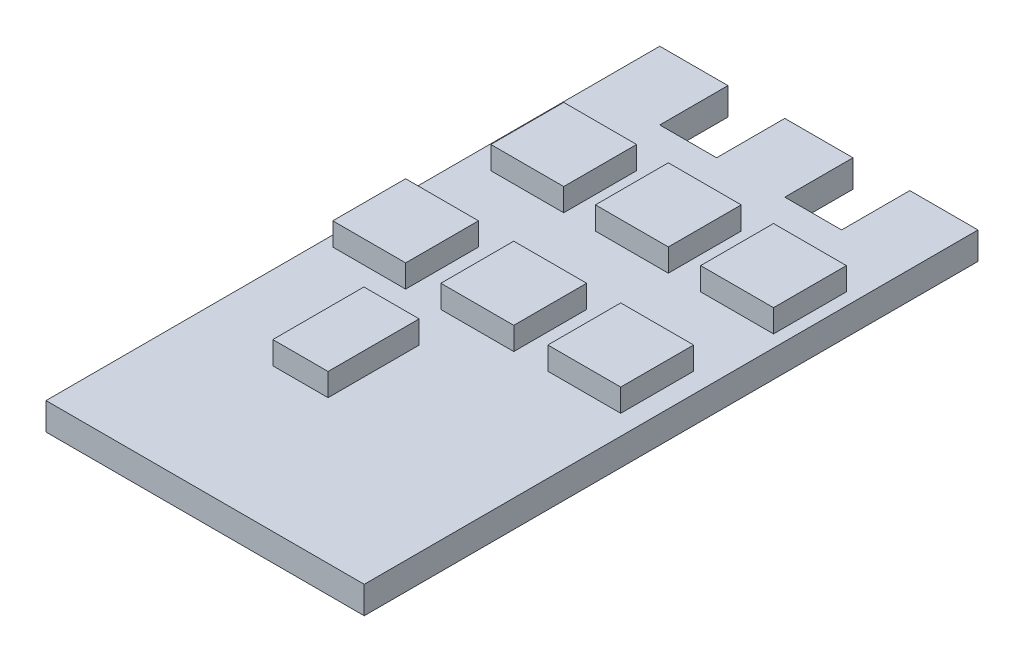
SolidWorks part; units mm, degrees
ref_plane "Front Plane" through (0, 0, 0) normal (0, 0, 1) x (1, 0, 0)
ref_plane "Top Plane" through (0, 0, 0) normal (0, 1, 0) x (1, 0, 0)
ref_plane "Right Plane" through (0, 0, 0) normal (1, 0, 0) x (0, 0, -1)
sketch "Sketch1" plane through (0, 0, 0) normal (0, 1, 0) x (1, 0, 0)
  line L0 (0, 21.6721) -> (0, -24.4888) construction
  line L1 (-7, 12) -> (7, 12)
  line L2 (-7, 12) -> (-7, -12)
  line L3 (-7, -12) -> (7, -12)
  line L4 (7, 12) -> (7, -12)
  line L5 (-7, 12) -> (7, -12) construction
  line L6 (-7, -12) -> (7, 12) construction
  line L8 (-1.5, 15) -> (1.5, 15)
  line L9 (-1.5, 15) -> (-1.5, 12)
  line L10 (-1.5, 12) -> (1.5, 12)
  line L11 (1.5, 15) -> (1.5, 12)
  line L12 (-1.5, 15) -> (1.5, 12) construction
  line L13 (-1.5, 12) -> (1.5, 15) construction
  line L14 (-7, 12) -> (-4, 12)
  line L15 (-7, 12) -> (-7, 15)
  line L16 (-7, 15) -> (-4, 15)
  line L17 (-4, 12) -> (-4, 15)
  line L18 (7, 12) -> (4, 12)
  line L19 (7, 12) -> (7, 15)
  line L20 (7, 15) -> (4, 15)
  line L21 (4, 12) -> (4, 15)
  point P0 (0, 0)
  point P7 (0, 13.5)
  dimension "D1" = 24
  dimension "D2" = 14
  dimension "D3" = 3
  dimension "D4" = 3
extrude "PCB" add sketch "Sketch1" along normal blind 1.2 contours L4 L1 L2 L3 | L1 L17 L16 L15 | L11 L8 L9 L1 | L21 L1 L19 L20 region at (-5.5, 0, -13.5) region at (0, 0, 0) region at (0, 0, -13.5) region at (5.5, 0, -13.5)
sketch "Sketch2" plane through (0, 1.2, 0) normal (0, 1, 0) x (1, 0, 0)
  line L1 (-5.9719, 9.747) -> (-2.7662, 9.747)
  line L2 (-5.9719, 9.747) -> (-5.9719, 6.5413)
  line L3 (-5.9719, 6.5413) -> (-2.7662, 6.5413)
  line L4 (-2.7662, 9.747) -> (-2.7662, 6.5413)
  line L5 (-1.3702, 9.747) -> (1.8355, 9.747)
  line L6 (-1.3702, 9.747) -> (-1.3702, 6.5413)
  line L7 (-1.3702, 6.5413) -> (1.8355, 6.5413)
  line L8 (1.8355, 9.747) -> (1.8355, 6.5413)
  line L9 (3.2574, 9.747) -> (6.4631, 9.747)
  line L10 (3.2574, 9.747) -> (3.2574, 6.5413)
  line L11 (3.2574, 6.5413) -> (6.4631, 6.5413)
  line L12 (6.4631, 9.747) -> (6.4631, 6.5413)
  line L13 (-3.335, 3.3614) -> (-6.5407, 3.3614)
  line L14 (-3.335, 3.3614) -> (-3.335, 0.1557)
  line L15 (-3.335, 0.1557) -> (-6.5407, 0.1557)
  line L16 (-6.5407, 3.3614) -> (-6.5407, 0.1557)
  line L17 (-1.7838, 3.3614) -> (1.4219, 3.3614)
  line L18 (-1.7838, 3.3614) -> (-1.7838, 0.1557)
  line L19 (-1.7838, 0.1557) -> (1.4219, 0.1557)
  line L20 (1.4219, 3.3614) -> (1.4219, 0.1557)
  line L21 (2.9213, 3.3614) -> (6.1271, 3.3614)
  line L22 (2.9213, 3.3614) -> (2.9213, 0.1557)
  line L23 (2.9213, 0.1557) -> (6.1271, 0.1557)
  line L24 (6.1271, 3.3614) -> (6.1271, 0.1557)
  line L25 (-3.335, -1.6799) -> (-0.9048, -1.6799)
  line L26 (-3.335, -1.6799) -> (-3.335, -5.687)
  line L27 (-3.335, -5.687) -> (-0.9048, -5.687)
  line L28 (-0.9048, -1.6799) -> (-0.9048, -5.687)
extrude "Top components" add sketch "Sketch2" along normal blind 1
sketch "Sketch3" plane through (0, 0, 0) normal (0, -1, 0) x (1, 0, 0)
  line L1 (-2.7921, 0) -> (1.2409, 0)
  line L2 (-2.7921, 0) -> (-2.7921, 4.0583)
  line L3 (-2.7921, 4.0583) -> (1.2409, 4.0583)
  line L4 (1.2409, 0) -> (1.2409, 4.0583)
  line L5 (-5.8944, -3.9818) -> (-2.7921, -3.9818)
  line L6 (-5.8944, -3.9818) -> (-5.8944, -6.9032)
  line L7 (-5.8944, -6.9032) -> (-2.7921, -6.9032)
  line L8 (-2.7921, -3.9818) -> (-2.7921, -6.9032)
  line L9 (-1.3185, -3.9818) -> (1.4995, -3.9818)
  line L10 (-1.3185, -3.9818) -> (-1.3185, -6.9032)
  line L11 (-1.3185, -6.9032) -> (1.4995, -6.9032)
  line L12 (1.4995, -3.9818) -> (1.4995, -6.9032)
  line L13 (3.0765, -3.9818) -> (5.9461, -3.9818)
  line L14 (3.0765, -3.9818) -> (3.0765, -6.9032)
  line L15 (3.0765, -6.9032) -> (5.9461, -6.9032)
  line L16 (5.9461, -3.9818) -> (5.9461, -6.9032)
  line L17 (3.516, 9.4874) -> (5.3515, 9.4874)
  line L18 (3.516, 9.4874) -> (3.516, 6.3592)
  line L19 (3.516, 6.3592) -> (5.3515, 6.3592)
  line L20 (5.3515, 9.4874) -> (5.3515, 6.3592)
extrude "Bottom components" add sketch "Sketch3" along normal blind 1
